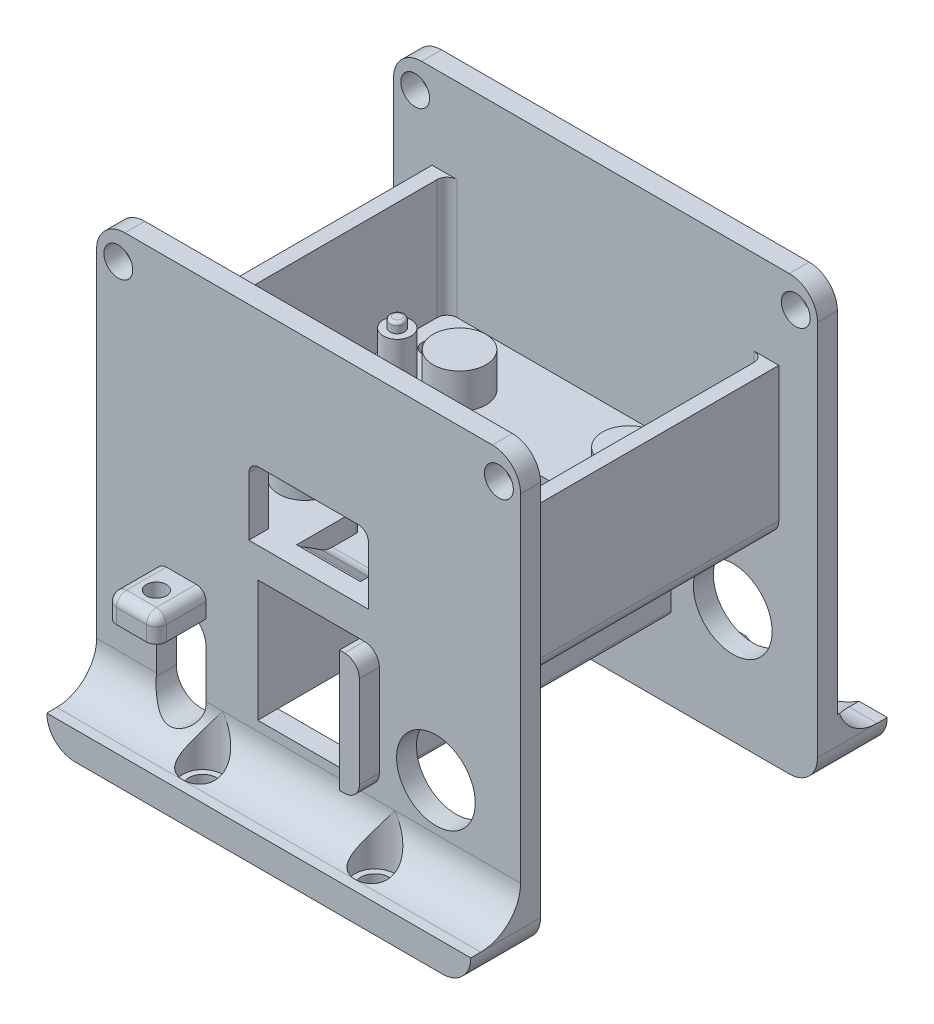
SolidWorks part; units mm, degrees
other "标注1"
sketch "草图55" plane through (-21.28, -20, 20.9) normal (0, 0, 1) x (1, 0, 0)
material "尼龙 101"
ref_plane "前视基准面" through (0, 0, 0) normal (0, 0, 1) x (1, 0, 0)
ref_plane "上视基准面" through (0, 0, 0) normal (0, 1, 0) x (1, 0, 0)
ref_plane "右视基准面" through (0, 0, 0) normal (1, 0, 0) x (0, 0, -1)
other "Configuration Table"
sketch "草图1" plane through (0, 0, 0) normal (0, 1, 0) x (1, 0, 0)
  line L1 (-15.9, 13.9) -> (15.9, 13.9)
  line L2 (-15.9, 13.9) -> (-15.9, -13.9)
  line L3 (-15.9, -13.9) -> (15.9, -13.9)
  line L4 (15.9, 13.9) -> (15.9, -13.9)
  line L5 (-15.9, 13.9) -> (15.9, -13.9) construction
  line L6 (-15.9, -13.9) -> (15.9, 13.9) construction
  point P0 (0, 0)
  dimension "D1" = 31.8
  dimension "D2" = 27.8
extrude "凸台-拉伸1" add sketch "草图1" along normal blind 3
sketch "草图2" plane through (0, 3, 0) normal (0, 1, 0) x (1, 0, 0)
  line L0 (0, 0) -> (0, 5.35) construction
  line L1 (-5.35, 5.35) -> (5.35, 5.35)
  line L2 (5.35, 5.35) -> (5.35, -7.55)
  line L3 (5.35, -7.55) -> (4.35, -7.55)
  line L4 (4.35, -7.55) -> (4.35, 4.35)
  line L5 (4.35, 4.35) -> (-4.35, 4.35)
  line L6 (-4.35, -7.55) -> (-4.35, 4.35)
  line L7 (-5.35, -7.55) -> (-4.35, -7.55)
  line L8 (-5.35, 5.35) -> (-5.35, -7.55)
  point P9 (0, 4.35)
  dimension "D1" = 8.7
  dimension "D2" = 11.9
  dimension "D3" = 4.35
  dimension "D4" = 1
  dimension "D5" = 1
extrude "凸台-拉伸2" add sketch "草图2" along normal blind 1.5
sketch "草图5" plane through (0, 3, 0) normal (0, 1, 0) x (1, 0, 0)
  line L0 (0, 13.9) -> (0, 0) construction
  line L1 (15.9, 13.9) -> (-15.9, 13.9) construction
  line L2 (0, 0) -> (15.9, 0) construction
  line L3 (15.9, -13.9) -> (15.9, 13.9) construction
  circle A0 centre (12.5, 5.5) radius 1.4
  circle A1 centre (12.5, -5.5) radius 1.4
  circle A2 centre (-12.5, -5.5) radius 1.4
  circle A3 centre (-12.5, 5.5) radius 1.4
  dimension "D1" = 2.8
  dimension "D2" = 25
  dimension "D3" = 11
extrude "凸台-拉伸3" add sketch "草图5" along normal blind 4.5
sketch "草图6" plane through (0, 7.5, 0) normal (0, 1, 0) x (1, 0, 0)
  circle A0 centre (-12.5, -5.5) radius 0.725
  circle A1 centre (-12.5, 5.5) radius 0.725
  circle A2 centre (12.5, 5.5) radius 0.725
  circle A3 centre (12.5, -5.5) radius 0.725
  dimension "D1" = 1.45
extrude "凸台-拉伸4" add sketch "草图6" along normal blind 1
sketch "草图7" plane through (0, 3, 0) normal (0, 1, 0) x (1, 0, 0)
  line L0 (0, 0) -> (0, 13.9) construction
  line L1 (15.9, 13.9) -> (-15.9, 13.9) construction
  line L2 (0, 0) -> (15.9, 0) construction
  line L3 (15.9, -13.9) -> (15.9, 13.9) construction
  circle A0 centre (13.5, 10) radius 1
  circle A1 centre (-13.5, 10) radius 1
  circle A2 centre (-13.5, -10) radius 1
  circle A3 centre (13.5, -10) radius 1
  dimension "D1" = 2
  dimension "D2" = 20
  dimension "D3" = 27
extrude "切除-拉伸1" cut sketch "草图7" against normal blind 10
sketch "草图8" plane through (0, 0, 0) normal (0, -1, 0) x (1, 0, 0)
  circle A0 centre (-13.5, 10) radius 2
  circle A1 centre (13.5, 10) radius 2
  circle A2 centre (13.5, -10) radius 2
  circle A3 centre (-13.5, -10) radius 2
  dimension "D1" = 4
extrude "切除-拉伸2" cut sketch "草图8" against normal blind 1
fillet "圆角1" radius 1 4 edges at (-15.9, 1.5, -13.9) (15.9, 1.5, -13.9) (-15.9, 1.5, 13.9) (15.9, 1.5, 13.9)
sketch "草图9" plane through (0, 3, 0) normal (0, 1, 0) x (1, 0, 0)
  line L0 (0, 13.9) -> (0, 0) construction
  line L1 (14.9, 13.9) -> (-14.9, 13.9) construction
  line L2 (0, 0) -> (15.9, 0) construction
  line L3 (15.9, -12.9) -> (15.9, 12.9) construction
  circle A0 centre (8.5, 7.75) radius 2.65
  circle A1 centre (-8.5, 7.75) radius 2.65
  circle A2 centre (-8.5, -7.75) radius 2.65
  circle A3 centre (8.5, -7.75) radius 2.65
  dimension "D1" = 17
  dimension "D2" = 15.5
  dimension "D3" = 5.3
extrude "凸台-拉伸5" add sketch "草图9" along normal blind 3.5
fillet "圆角2" radius 0.3 4 edges at (12.5, 8.5, -4.775) (12.5, 8.5, 6.225) (-12.5, 8.5, 6.225) (-12.5, 8.5, -4.775)
sketch "草图15" plane through (0, 3, 0) normal (0, 1, 0) x (1, 0, 0)
  line L0 (0, 0) -> (0, 13.9) construction
  line L1 (14.9, 13.9) -> (-14.9, 13.9) construction
  line L2 (-4.35, 4.35) -> (4.35, 4.35)
  line L3 (4.35, 4.35) -> (4.35, -7.55)
  line L4 (4.35, -7.55) -> (3.2, -7.55)
  line L5 (3.2, -7.55) -> (3.2, -13.9)
  line L6 (-14.9, -13.9) -> (14.9, -13.9) construction
  line L7 (3.2, -13.9) -> (-3.2, -13.9)
  line L8 (-3.2, -7.55) -> (-3.2, -13.9)
  line L9 (-4.35, -7.55) -> (-3.2, -7.55)
  line L10 (-4.35, 4.35) -> (-4.35, -7.55)
  line L11 (4.35, 4.35) -> (4.35, -7.55) construction
  point P14 (0, -13.9)
  point P17 (0, 4.35)
  dimension "D1" = 6.4
extrude "切除-拉伸8" cut sketch "草图15" against normal blind 2
sketch "草图17" plane through (0, 4.5, 0) normal (0, 1, 0) x (1, 0, 0)
  line L8 (-4.35, -7.55) -> (-4.35, 4.35)
  line L9 (-4.35, 4.35) -> (4.35, 4.35)
  line L10 (4.35, 4.35) -> (4.35, -7.55)
  line L11 (4.35, -7.55) -> (5.35, -7.55)
  line L12 (5.35, -7.55) -> (5.35, 5.35)
  line L13 (5.35, 5.35) -> (-5.35, 5.35)
  line L14 (-5.35, 5.35) -> (-5.35, -7.55)
  line L15 (-5.35, -7.55) -> (-4.35, -7.55)
  line L16 (-4.35, -7.55) -> (-4.35, 4.35)
  line L17 (-4.35, 4.35) -> (4.35, 4.35)
  line L18 (4.35, 4.35) -> (4.35, -7.55)
  line L19 (4.35, -7.55) -> (5.35, -7.55)
  line L20 (5.35, -7.55) -> (5.35, 5.35)
  line L21 (5.35, 5.35) -> (-5.35, 5.35)
  line L22 (-5.35, 5.35) -> (-5.35, -7.55)
  line L23 (-5.35, -7.55) -> (-4.35, -7.55)
  dimension "D1" = 0
extrude "切除-拉伸9" cut sketch "草图17" against normal blind 1.5
sketch "草图18" plane through (3.2, 0, 0) normal (-1, 0, 0) x (0, 0, 1)
  line L0 (13.9, 1) -> (10.9, 1)
  line L2 (13.9, 1) -> (13.9, 3) construction
  line L3 (13.9, 2.6) -> (13.9, 1)
  line L5 (13.9, 3) -> (13.9, 0) construction
  line L6 (13.9, 2.6) -> (13.4, 2.6)
  line L7 (13.4, 2.6) -> (10.9, 1)
  line L8 (13.9, 3) -> (12.9, 3) construction
  dimension "D1" = 3
  dimension "D2" = 0.4
  dimension "D3" = 0.5
extrude "凸台-拉伸6" add sketch "草图18" along normal up to surface (6.4 mm away) up to face at (-3.2, 2, 10.725)
fillet "圆角3" radius 2 1 edges at (0, 1, 10.9)
fillet "圆角5" radius 1 1 edges at (0, 2.6, 13.4)
fillet "圆角6" radius 0.4 2 edges at (3.2, 2, 7.55) (-3.2, 2, 7.55)
sketch "草图21" plane through (0, 0, 0) normal (0, -1, 0) x (1, 0, 0)
  line L0 (-14.9, 13.9) -> (14.9, 13.9) construction
  line L1 (-15.9, -12.9) -> (-15.9, 12.9) construction
  line L2 (14.9, -13.9) -> (-14.9, -13.9) construction
  line L3 (15.9, 12.9) -> (15.9, -12.9) construction
  line L4 (-14.9, 13.9) -> (14.9, 13.9)
  line L5 (-15.9, -12.9) -> (-15.9, 12.9)
  line L6 (14.9, -13.9) -> (-14.9, -13.9)
  line L7 (15.9, 12.9) -> (15.9, -12.9)
  line L9 (-17.4, 15.9) -> (17.4, 15.9)
  line L10 (-17.4, 15.9) -> (-17.4, -15.9)
  line L11 (-17.4, -15.9) -> (17.4, -15.9)
  line L12 (17.4, 15.9) -> (17.4, -15.9)
  arc A0 (15.9, 12.9) -> (14.9, 13.9) centre (14.9, 12.9) ccw construction
  arc A1 (-14.9, 13.9) -> (-15.9, 12.9) centre (-14.9, 12.9) ccw construction
  arc A2 (-15.9, -12.9) -> (-14.9, -13.9) centre (-14.9, -12.9) ccw construction
  arc A3 (14.9, -13.9) -> (15.9, -12.9) centre (14.9, -12.9) ccw construction
  arc A4 (15.9, 12.9) -> (14.9, 13.9) centre (14.9, 12.9) ccw
  arc A5 (-14.9, 13.9) -> (-15.9, 12.9) centre (-14.9, 12.9) ccw
  arc A6 (-15.9, -12.9) -> (-14.9, -13.9) centre (-14.9, -12.9) ccw
  arc A7 (14.9, -13.9) -> (15.9, -12.9) centre (14.9, -12.9) ccw
  dimension "D1" = 1.5
  dimension "D2" = 1.5
  dimension "D3" = 2
  dimension "D4" = 2
extrude "凸台-拉伸7" add sketch "草图21" against normal blind 15
sketch "草图22" plane through (0, 0, 15.9) normal (0, 0, 1) x (1, 0, 0)
  line L2 (-21.28, 0) -> (-21.28, 20.67)
  line L3 (-18.45, 23.5) -> (18.45, 23.5)
  line L4 (21.28, 0) -> (21.28, 20.67)
  line L5 (-21.28, 0) -> (21.28, 23.5) construction
  line L6 (-21.28, 23.5) -> (21.28, 0) construction
  line L7 (0, 0) -> (0, 23.5) construction
  line L10 (-21.28, 0) -> (-21.28, -17.17)
  line L11 (-18.45, -20) -> (18.45, -20)
  line L12 (21.28, 0) -> (21.28, -17.17)
  arc A0 (-21.28, 20.67) -> (-18.45, 23.5) centre (-18.45, 20.67) cw
  arc A1 (18.45, 23.5) -> (21.28, 20.67) centre (18.45, 20.67) cw
  arc A4 (18.45, -20) -> (21.28, -17.17) centre (18.45, -17.17) ccw
  arc A5 (-21.28, -17.17) -> (-18.45, -20) centre (-18.45, -17.17) ccw
  circle A6 centre (-19.1, 20.67) radius 1.45
  circle A7 centre (19.1, 20.67) radius 1.45
  point P4 (0, 11.75)
  point P22 (21.28, -20)
  dimension "D3" = 2.83
  dimension "D4" = 2.83
  dimension "D8" = 2.83
  dimension "D1" = 42.56
  dimension "D2" = 23.5
  dimension "D7" = 20
extrude "凸台-拉伸8" add sketch "草图22" against normal blind 2
sketch "草图24" plane through (0, 0, -15.9) normal (0, 0, -1) x (-1, 0, 0)
  line L5 (-18.45, -20) -> (18.45, -20)
  line L6 (-18.45, -20) -> (18.45, -20)
  line L21 (21.28, -17.17) -> (21.28, 20.67)
  line L22 (18.45, 23.5) -> (-18.45, 23.5)
  line L23 (-21.28, 20.67) -> (-21.28, -17.17)
  line L37 (21.28, -17.17) -> (21.28, 20.67)
  line L38 (18.45, 23.5) -> (-18.45, 23.5)
  line L39 (-21.28, 20.67) -> (-21.28, -17.17)
  circle A0 centre (18.45, 20.67) radius 0.65 construction
  circle A1 centre (-18.45, 20.67) radius 0.65 construction
  arc A2 (21.28, 20.67) -> (18.45, 23.5) centre (18.45, 20.67) ccw
  arc A3 (-18.45, 23.5) -> (-21.28, 20.67) centre (-18.45, 20.67) ccw
  arc A4 (21.28, 20.67) -> (18.45, 23.5) centre (18.45, 20.67) ccw
  arc A5 (-18.45, 23.5) -> (-21.28, 20.67) centre (-18.45, 20.67) ccw
  circle A8 centre (-19.1, 20.67) radius 1.45
  circle A9 centre (19.1, 20.67) radius 1.45
  arc A12 (-21.28, -17.17) -> (-18.45, -20) centre (-18.45, -17.17) ccw
  arc A13 (-21.28, -17.17) -> (-18.45, -20) centre (-18.45, -17.17) ccw
  arc A14 (18.45, -20) -> (21.28, -17.17) centre (18.45, -17.17) ccw
  arc A15 (18.45, -20) -> (21.28, -17.17) centre (18.45, -17.17) ccw
  dimension "D1" = 0
extrude "凸台-拉伸9" add sketch "草图24" against normal blind 2
sketch "草图25" plane through (0, 0, 15.9) normal (0, 0, 1) x (1, 0, 0)
  line L1 (-5, 9.85) -> (5, 9.85)
  line L2 (-6, 8.85) -> (-6, 3)
  line L4 (6, 8.85) -> (6, 3)
  line L5 (-6, 3) -> (6, 3)
  line L9 (-6, 3) -> (6, 9.85) construction
  arc A0 (5, 9.85) -> (6, 8.85) centre (5, 8.85) cw
  arc A1 (-5, 9.85) -> (-6, 8.85) centre (-5, 8.85) ccw
  point P5 (6, 9.85)
  point P8 (0, 6.425)
  point P9 (-6, 9.85)
  dimension "D2" = 1
  dimension "D1" = 12
extrude "切除-拉伸10" cut sketch "草图25" against normal blind 2
sketch "草图27" plane through (0, 0, 15.9) normal (0, 0, 1) x (1, 0, 0)
  line L0 (-5.1, 0) -> (5.1, -12.2) construction
  line L5 (-5.1, 0) -> (5.1, 0) construction
  line L16 (-17.4, 0) -> (17.4, 0) construction
  line L18 (-5.1, 0) -> (-5.1, -12.2)
  line L20 (5.1, 0) -> (5.1, -12.2)
  line L21 (-6.6, 0) -> (-6.6, -11.7)
  line L26 (6.6, 0) -> (6.6, -11.7)
  line L31 (-6.6, 0) -> (-5.1, 0)
  line L33 (-6.1, -12.2) -> (-5.1, -12.2)
  line L34 (-6.6, 1.5) -> (6.6, 1.5) construction
  line L35 (0, 0) -> (0, -4.0507) construction
  line L36 (6.6, 1.5) -> (6.6, -13.7) construction
  line L37 (-6.6, 1.5) -> (-6.6, -13.7) construction
  line L38 (5.1, 0) -> (6.6, 0)
  line L39 (-6.6, -13.7) -> (6.6, -13.7) construction
  line L40 (-5.1, -12.2) -> (5.1, -12.2) construction
  line L41 (5.1, -12.2) -> (6.1, -12.2)
  arc A4 (6.1, -12.2) -> (6.6, -11.7) centre (6.1, -11.7) ccw
  arc A5 (-6.6, -11.7) -> (-6.1, -12.2) centre (-6.1, -11.7) ccw
  point P6 (-2.5, 0)
  point P7 (6.9808, -17.5163)
  point P19 (6.6, -12.2)
  point P24 (0, -6.1)
  dimension "D4" = 0.5
  dimension "D1" = 10.2
  dimension "D2" = 12.2
  dimension "D3" = 1.5
extrude "凸台-拉伸10" add sketch "草图27" against normal up to surface (29.8 mm away) up to face at (0, 8.25, -13.9)
sketch "草图35" plane through (0, 0, 15.9) normal (0, 0, 1) x (1, 0, 0)
  line L1 (-5.1, 0) -> (5.1, 0)
  line L2 (-5.1, 0) -> (-5.1, -12.2)
  line L3 (-5.1, -12.2) -> (5.1, -12.2)
  line L4 (5.1, 0) -> (5.1, -12.2)
extrude "切除-拉伸14" cut sketch "草图35" against normal through all
sketch "草图43" plane through (0, 0, 15.9) normal (0, 0, 1) x (1, 0, 0)
  line L0 (-21.28, -17.17) -> (21.28, -17.17)
  line L1 (-18.45, -20) -> (18.45, -20) construction
  line L2 (-18.45, -20) -> (18.45, -20)
  arc A1 (18.45, -20) -> (21.28, -17.17) centre (18.45, -17.17) ccw construction
  arc A3 (-21.28, -17.17) -> (-18.45, -20) centre (-18.45, -17.17) ccw construction
  arc A4 (18.45, -20) -> (21.28, -17.17) centre (18.45, -17.17) ccw
  arc A5 (-21.28, -17.17) -> (-18.45, -20) centre (-18.45, -17.17) ccw
extrude "凸台-拉伸14" add sketch "草图43" along normal blind 5
sketch "草图44" plane through (-21.28, 0, 0) normal (-1, 0, 0) x (0, 0, 1)
  line L3 (15.9, -13.17) -> (15.9, -17.17)
  line L4 (15.9, -17.17) -> (19.9, -17.17)
  arc A0 (19.9, -17.17) -> (15.9, -13.17) centre (19.9, -13.17) cw
  point P8 (15.9, -17.17)
  dimension "D1" = 4
extrude "凸台-拉伸15" add sketch "草图44" against normal up to surface (42.56 mm away) up to face at (21.28, 1.75, 14.9)
sketch "草图45" plane through (0, 0, -15.9) normal (0, 0, -1) x (-1, 0, 0)
  line L0 (-18.45, -20) -> (18.45, -20) construction
  line L1 (-21.28, -17.17) -> (21.28, -17.17) construction
  line L2 (-18.45, -20) -> (18.45, -20)
  line L3 (-21.28, -17.17) -> (21.28, -17.17)
  arc A0 (-21.28, -17.17) -> (-18.45, -20) centre (-18.45, -17.17) ccw construction
  arc A1 (18.45, -20) -> (21.28, -17.17) centre (18.45, -17.17) ccw construction
  arc A2 (-21.28, -17.17) -> (-18.45, -20) centre (-18.45, -17.17) ccw
  arc A3 (18.45, -20) -> (21.28, -17.17) centre (18.45, -17.17) ccw
extrude "凸台-拉伸16" add sketch "草图45" along normal blind 5
sketch "草图46" plane through (21.28, 0, 0) normal (1, 0, 0) x (0, 0, -1)
  line L0 (15.9, -13.17) -> (15.9, -17.17)
  line L1 (15.9, -17.17) -> (19.9, -17.17)
  arc A0 (15.9, -13.17) -> (19.9, -17.17) centre (19.9, -13.17) ccw
  point P7 (15.9, -17.17)
  dimension "D1" = 4
extrude "凸台-拉伸17" add sketch "草图46" against normal up to surface (42.56 mm away) up to face at (-21.28, 1.75, -14.9)
sketch "草图36" plane through (0, 0, 15.9) normal (0, 0, 1) x (1, 0, 0)
  line L0 (-5.1, 0) -> (5.1, -12.2) construction
  line L1 (5.1, 0) -> (-5.1, -12.2) construction
  line L2 (-5.1, -12.2) -> (5.1, -12.2) construction
  line L3 (-5.1, 0) -> (-5.1, -12.2) construction
  line L6 (-5.1, -12.2) -> (-5.1, -13.2) construction
  line L7 (-5.1, -13.2) -> (22.8364, -13.2) construction
  line L8 (21.28, -13.17) -> (21.28, 20.67) construction
  line L10 (-15.28, -8.4815) -> (-15.28, -13.4815)
  line L12 (-10.28, -13.4815) -> (-10.28, -8.4815)
  circle A0 centre (0, -6.1) radius 4.5 construction
  circle A3 centre (12.78, -8.4815) radius 8.5 construction
  circle A6 centre (12.78, -8.4815) radius 5.75 construction
  circle A7 centre (12.78, -8.4815) radius 3.95
  arc A9 (-10.28, -8.4815) -> (-15.28, -8.4815) centre (-12.78, -8.4815) ccw
  arc A11 (-15.28, -13.4815) -> (-10.28, -13.4815) centre (-12.78, -13.4815) ccw
  point P11 (0, -6.1)
  dimension "D1" = 9
  dimension "D2" = 17
  dimension "D3" = 7.9
  dimension "D4" = 9
  dimension "D5" = 11.5
extrude "切除-拉伸15" cut sketch "草图36" against normal through all both and the other way through all
sketch "草图37" plane through (0, 0, 15.9) normal (0, 0, 1) x (1, 0, 0)
  line L0 (-15.28, -5.9815) -> (-15.28, -3.4815)
  line L1 (-15.28, -3.4815) -> (-10.28, -3.4815)
  line L2 (-10.28, -3.4815) -> (-10.28, -5.9815)
  line L3 (-15.28, -5.9815) -> (-10.28, -5.9815)
extrude "凸台-拉伸11" add sketch "草图37" along normal blind 5
sketch "草图38" plane through (0, 0, -15.9) normal (0, 0, -1) x (-1, 0, 0)
  line L0 (15.28, -3.4815) -> (15.28, -5.9815) construction
  line L1 (10.28, -5.9815) -> (10.28, -3.4815) construction
  line L2 (10.28, -3.4815) -> (15.28, -3.4815) construction
  line L3 (15.28, -3.4815) -> (15.28, -5.9815)
  line L4 (10.28, -5.9815) -> (10.28, -3.4815)
  line L5 (10.28, -3.4815) -> (15.28, -3.4815)
  line L6 (10.28, -5.9815) -> (15.28, -5.9815)
extrude "凸台-拉伸12" add sketch "草图38" along normal blind 5
fillet "圆角7" radius 1 2 edges at (-10.28, -4.7315, 20.9) (-15.28, -4.7315, 20.9)
fillet "圆角8" radius 1 2 edges at (-10.28, -4.7315, -20.9) (-15.28, -4.7315, -20.9)
sketch "草图41" plane through (0, 0, 15.9) normal (0, 0, 1) x (1, 0, 0)
  line L1 (5.1, 0) -> (5.6, 0)
  line L2 (5.1, 0) -> (5.1, -12.2)
  line L3 (5.1, -12.2) -> (5.6, -12.2)
  line L4 (7.1, -1.5) -> (7.1, -10.7)
  arc A0 (5.6, -12.2) -> (7.1, -10.7) centre (5.6, -10.7) ccw
  arc A1 (7.1, -1.5) -> (5.6, 0) centre (5.6, -1.5) ccw
  dimension "D1" = 1.5
  dimension "D2" = 2
extrude "凸台-拉伸13" add sketch "草图41" along normal blind 2
sketch "草图42" plane through (0, -3.4815, 0) normal (0, 1, 0) x (1, 0, 0)
  line L0 (-14.9871, 20.6071) -> (-10.28, 15.9) construction
  line L1 (-15.28, -15.9) -> (-10.5729, -20.6071) construction
  line L2 (-10.5729, 20.6071) -> (-15.28, 15.9) construction
  line L3 (-10.28, -15.9) -> (-14.9871, -20.6071) construction
  arc A0 (-14.28, 20.9) -> (-15.28, 19.9) centre (-14.28, 19.9) ccw construction
  arc A1 (-10.28, 19.9) -> (-11.28, 20.9) centre (-11.28, 19.9) ccw construction
  arc A2 (-11.28, -20.9) -> (-10.28, -19.9) centre (-11.28, -19.9) ccw construction
  arc A3 (-15.28, -19.9) -> (-14.28, -20.9) centre (-14.28, -19.9) ccw construction
  circle A4 centre (-12.78, -18.4) radius 1
  circle A5 centre (-12.78, 18.4) radius 1
  point P24 (-12.78, 18.4)
  point P25 (-12.78, -18.4)
  dimension "D1" = 2
  dimension "D2" = 2
sketch "草图49" plane through (0, -20, 0) normal (0, -1, 0) x (1, 0, 0)
  line L5 (8.64, 17.89) -> (-8.64, -17.89) construction
  line L6 (-8.64, 17.89) -> (8.64, 17.89) construction
  line L7 (-8.64, 17.89) -> (-8.64, -17.89) construction
  line L8 (-8.64, -17.89) -> (8.64, -17.89) construction
  line L9 (8.64, 17.89) -> (8.64, -17.89) construction
  circle A1 centre (-8.64, 17.89) radius 1.4
  circle A2 centre (8.64, 17.89) radius 1.4
  circle A3 centre (8.64, -17.89) radius 1.4
  circle A4 centre (-8.64, -17.89) radius 1.4
  point P6 (0, 0)
  dimension "D1" = 17.28
  dimension "D2" = 35.78
extrude "切除-拉伸17" cut sketch "草图49" against normal blind 6
sketch "草图51" plane through (0, 0, -15.9) normal (0, 0, -1) x (-1, 0, 0)
  circle A3 centre (-12.78, -8.4815) radius 10.3764
extrude "切除-拉伸18" cut sketch "草图51" along normal blind 6
sketch "草图52" plane through (0, -17.17, 0) normal (0, 1, 0) x (1, 0, 0)
  circle A3 centre (-8.64, -17.89) radius 1.99
  circle A4 centre (-8.64, 17.89) radius 1.99
  circle A5 centre (8.64, 17.89) radius 1.99
  circle A6 centre (8.64, -17.89) radius 1.99
extrude "切除-拉伸19" cut sketch "草图52" against normal blind 1.5
extrude "切除-拉伸20" cut sketch "草图52<2>" along normal blind 4
sketch "草图52<2>" plane through (0, -17.17, 0) normal (0, 1, 0) x (1, 0, 0) same geometry as "草图52"
fillet "圆角10" radius 1 5 edges at (-14.9871, -3.4815, 20.6071) (-12.78, -3.4815, 20.9) (-10.5729, -3.4815, 20.6071) (-10.28, -3.4815, 17.9) (-15.28, -3.4815, 17.9)
fillet "圆角12" radius 1 5 edges at (-15.28, -3.4815, -17.9) (-14.9871, -3.4815, -20.6071) (-12.78, -3.4815, -20.9) (-10.5729, -3.4815, -20.6071) (-10.28, -3.4815, -17.9)
extrude "切除-拉伸21" cut sketch "草图42" against normal blind 4
ref_plane "基准面7" through (0, 0, -6.3) normal (0, 0, -1) x (-1, 0, 0)
sketch "草图54" plane through (0, 0, -6.3) normal (0, 0, -1) x (-1, 0, 0)
  line L0 (-5.1, 0) -> (5.1, -12.2) construction
  line L1 (-5.1, 0) -> (5.1, 0)
  line L2 (-5.1, 0) -> (-5.1, -12.2)
  line L3 (-5.1, -12.2) -> (5.1, -12.2)
  line L4 (5.1, 0) -> (5.1, -12.2)
  line L5 (0, -1.6) -> (0, -10.6) construction
  circle A0 centre (0, -1.6) radius 0.8
  circle A1 centre (0, -10.6) radius 0.8
  circle A2 centre (0, -6.1) radius 1.8
  point P8 (0, -6.1)
  point P11 (0, -6.1)
  dimension "D1" = 9
  dimension "D2" = 0
  dimension "D3" = 0
extrude "凸台-拉伸18" add sketch "草图54" along normal blind 2
fillet "圆角13" radius 1.5 2 edges at (17.4, 0, 0) (-17.4, 0, 0)
